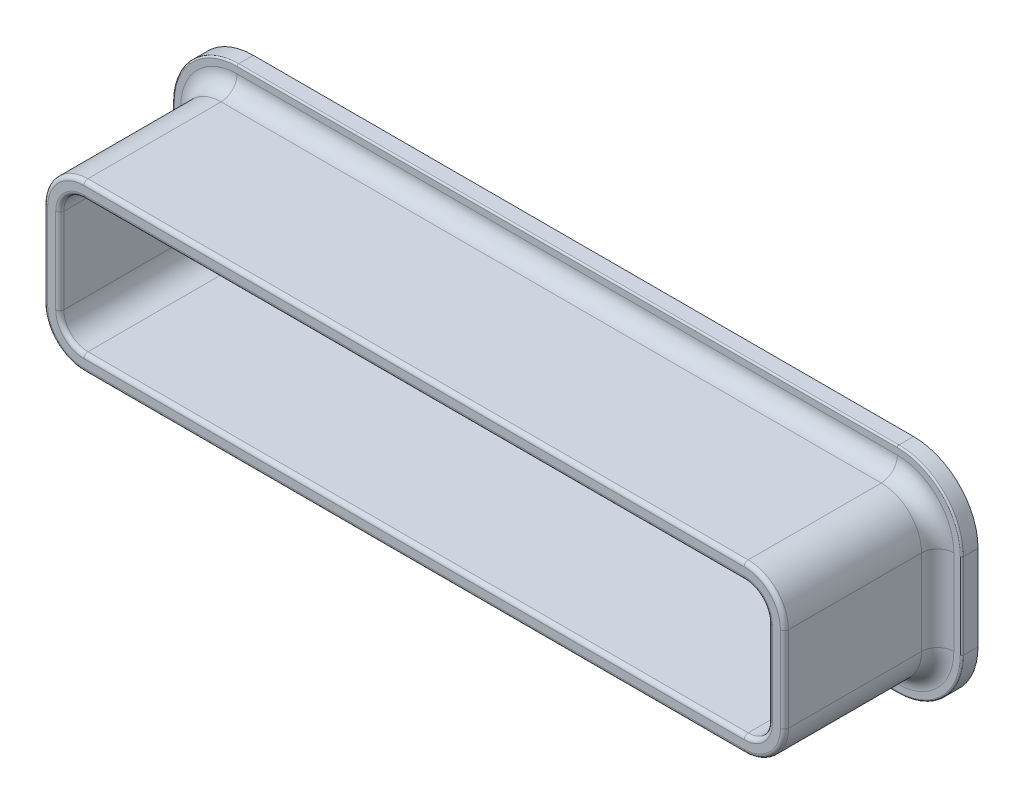
SolidWorks part; units mm, degrees
material "moto_grey"
ref_plane "Front Plane" through (0, 0, 0) normal (0, 0, 1) x (1, 0, 0)
ref_plane "Top Plane" through (0, 0, 0) normal (0, 1, 0) x (1, 0, 0)
ref_plane "Right Plane" through (0, 0, 0) normal (1, 0, 0) x (0, 0, -1)
sketch "Sketch1" plane through (0, 0, 0) normal (0, 0, 1) x (1, 0, 0)
  line L0 (-106.8351, 12.0388) -> (-138.6549, -19.781)
  line L5 (-145.726, -22.7099) -> (-171.5838, -22.7099)
  line L6 (12.5816, 19.7277) -> (-99.764, 19.7277)
  line L7 (12.5816, 14.9677) -> (-99.764, 14.9677)
  line L8 (-110.2009, 15.4046) -> (-142.0207, -16.4152)
  line L9 (-145.726, -17.9499) -> (-171.5838, -17.9499)
  line L10 (-171.5838, -17.9499) -> (-171.5838, -22.7099)
  line L11 (0, 0) -> (0, -7.765)
  line L12 (-133.0799, -14.206) -> (-133.0799, -22.8611)
  line L14 (171.5838, -17.9499) -> (171.5838, -22.7099)
  line L15 (145.726, -17.9499) -> (171.5838, -17.9499)
  line L16 (145.726, -22.7099) -> (171.5838, -22.7099)
  line L17 (110.2009, 15.4046) -> (142.0207, -16.4152)
  line L18 (106.8351, 12.0388) -> (138.6549, -19.781)
  line L19 (12.5816, 19.7277) -> (99.764, 19.7277)
  line L20 (12.5816, 14.9677) -> (99.764, 14.9677)
  line L21 (-133.0799, -22.8611) -> (133.0799, -22.8611)
  line L22 (133.0799, -22.8611) -> (133.0799, -14.206)
  line L23 (-1.1284, 10.8741) -> (80.7505, 10.8741)
  line L24 (-86.5735, -22.8611) -> (-82.4634, -22.8611)
  line L25 (-86.5735, -22.8611) -> (-86.5735, 8.8226)
  line L26 (-86.5735, 8.8226) -> (-82.4634, 8.8226)
  line L27 (-82.4634, -22.8611) -> (-82.4634, 8.8226)
  line L28 (-1.1284, 7.8741) -> (80.7505, 7.8741)
  line L29 (-6.1284, 2.8741) -> (-6.1284, -7.7099)
  line L30 (-1.1284, -12.7099) -> (80.7505, -12.7099)
  line L31 (85.7505, 2.8741) -> (85.7505, -7.7099)
  line L32 (-6.1284, 7.8741) -> (85.7505, -12.7099) construction
  line L33 (-6.1284, -12.7099) -> (85.7505, 7.8741) construction
  line L34 (88.7505, 2.8741) -> (88.7505, -7.7099)
  line L35 (-1.1284, -15.7099) -> (80.7505, -15.7099)
  line L36 (-9.1284, 2.8741) -> (-9.1284, -7.7099)
  arc A0 (-138.6549, -19.781) -> (-145.726, -22.7099) centre (-145.726, -12.7099) cw
  arc A1 (-106.8351, 12.0388) -> (-99.764, 14.9677) centre (-99.764, 4.9677) cw
  arc A2 (-110.2009, 15.4046) -> (-99.764, 19.7277) centre (-99.764, 4.9677) cw
  arc A3 (-142.0207, -16.4152) -> (-145.726, -17.9499) centre (-145.726, -12.7099) cw
  arc A4 (138.6549, -19.781) -> (145.726, -22.7099) centre (145.726, -12.7099) ccw
  arc A5 (142.0207, -16.4152) -> (145.726, -17.9499) centre (145.726, -12.7099) ccw
  arc A6 (106.8351, 12.0388) -> (99.764, 14.9677) centre (99.764, 4.9677) ccw
  arc A7 (110.2009, 15.4046) -> (99.764, 19.7277) centre (99.764, 4.9677) ccw
  arc A8 (80.7505, 7.8741) -> (85.7505, 2.8741) centre (80.7505, 2.8741) cw
  arc A9 (85.7505, -7.7099) -> (80.7505, -12.7099) centre (80.7505, -7.7099) cw
  arc A10 (-1.1284, -12.7099) -> (-6.1284, -7.7099) centre (-1.1284, -7.7099) cw
  arc A11 (-6.1284, 2.8741) -> (-1.1284, 7.8741) centre (-1.1284, 2.8741) cw
  arc A12 (80.7505, 10.8741) -> (88.7505, 2.8741) centre (80.7505, 2.8741) cw
  arc A13 (88.7505, -7.7099) -> (80.7505, -15.7099) centre (80.7505, -7.7099) cw
  arc A14 (-1.1284, -15.7099) -> (-9.1284, -7.7099) centre (-1.1284, -7.7099) cw
  arc A15 (-9.1284, 2.8741) -> (-1.1284, 10.8741) centre (-1.1284, 2.8741) cw
  point P0 (0, 0)
  point P9 (-141.5838, -22.7099)
  point P36 (0, -22.8611)
  point P44 (39.811, -2.4179)
  dimension "D3" = 10
  dimension "D6" = 5
  dimension "D1" = 135
  dimension "D2" = 30
  dimension "D5" = 45
  dimension "D4" = 4.76
  dimension "D7" = 3
extrude "Boss-Extrude1" add sketch "Sketch1" against normal blind 2 contours A15 L36 A14 L35 A13 L34 A12 L23 L29 A11 L28 A8 L31 A9 L30 A10 | A11 L29 A10 L30 A9 L31 A8 L28 region at (39.811, 9.8598, 0) region at (39.811, -2.4179, 0)
extrude "Boss-Extrude2" add sketch "Sketch1<6>" along normal blind 19 contours A11 L29 A10 L30 A9 L31 A8 L28 region at (39.811, -2.4179, 0)
sketch "Sketch1<6>" plane through (0, 0, 0) normal (0, 0, 1) x (1, 0, 0) same geometry as "Sketch1"
sketch "Sketch2" plane through (0, 0, 19) normal (0, 0, 1) x (1, 0, 0)
  line L8 (-4.1284, 2.8741) -> (-4.1284, -7.7099)
  line L9 (-1.1284, -10.7099) -> (80.7505, -10.7099)
  line L10 (83.7505, -7.7099) -> (83.7505, 2.8741)
  line L11 (80.7505, 5.8741) -> (-1.1284, 5.8741)
  line L12 (-4.1284, 2.8741) -> (-4.1284, -7.7099)
  line L13 (-1.1284, -10.7099) -> (80.7505, -10.7099)
  line L14 (83.7505, -7.7099) -> (83.7505, 2.8741)
  line L15 (80.7505, 5.8741) -> (-1.1284, 5.8741)
  arc A8 (-1.1284, 5.8741) -> (-4.1284, 2.8741) centre (-1.1284, 2.8741) ccw
  arc A9 (-4.1284, -7.7099) -> (-1.1284, -10.7099) centre (-1.1284, -7.7099) ccw
  arc A10 (80.7505, -10.7099) -> (83.7505, -7.7099) centre (80.7505, -7.7099) ccw
  arc A11 (83.7505, 2.8741) -> (80.7505, 5.8741) centre (80.7505, 2.8741) ccw
  arc A12 (-1.1284, 5.8741) -> (-4.1284, 2.8741) centre (-1.1284, 2.8741) ccw
  arc A13 (-4.1284, -7.7099) -> (-1.1284, -10.7099) centre (-1.1284, -7.7099) ccw
  arc A14 (80.7505, -10.7099) -> (83.7505, -7.7099) centre (80.7505, -7.7099) ccw
  arc A15 (83.7505, 2.8741) -> (80.7505, 5.8741) centre (80.7505, 2.8741) ccw
  dimension "D1" = 2
extrude "Cut-Extrude1" cut sketch "Sketch2" against normal blind 32
fillet "Fillet1" radius 0.5 16 edges at (39.811, 7.8741, 19) (84.286, 6.4096, 19) (85.7505, -2.4179, 19) (84.286, -11.2455, 19) (39.811, -12.7099, 19) (-4.664, -11.2455, 19) (-6.1284, -2.4179, 19) (-4.664, 6.4096, 19) (-4.1284, -2.4179, 19) (-3.2497, -9.8312, 19) (39.811, -10.7099, 19) (82.8718, -9.8312, 19) (83.7505, -2.4179, 19) (82.8718, 4.9954, 19) (39.811, 5.8741, 19) (-3.2497, 4.9954, 19)
fillet "Fillet2" radius 2 8 edges at (-4.664, 6.4096, 0) (-6.1284, -2.4179, 0) (-4.664, -11.2455, 0) (39.811, -12.7099, 0) (84.286, -11.2455, 0) (85.7505, -2.4179, 0) (84.286, 6.4096, 0) (39.811, 7.8741, 0)
fillet "Fillet3" radius 2 8 edges at (-3.2497, -9.8312, -2) (-4.1284, -2.4179, -2) (-3.2497, 4.9954, -2) (39.811, 5.8741, -2) (82.8718, 4.9954, -2) (83.7505, -2.4179, -2) (82.8718, -9.8312, -2) (39.811, -10.7099, -2)
fillet "Fillet4" radius 0.2 8 edges at (-6.7853, 8.5309, 0) (-9.1284, -2.4179, 0) (-6.7853, -13.3668, 0) (39.811, -15.7099, 0) (86.4073, -13.3668, 0) (88.7505, -2.4179, 0) (86.4073, 8.5309, 0) (39.811, 10.8741, 0)
